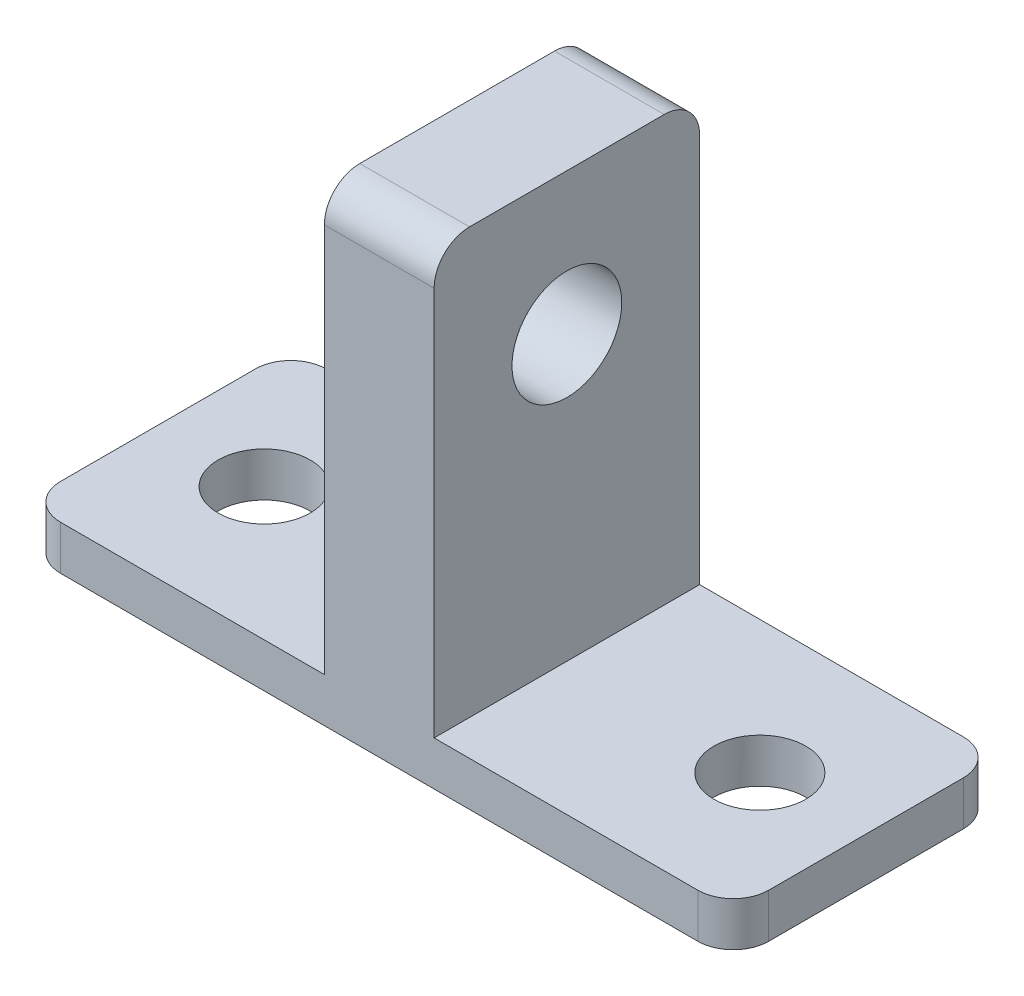
SolidWorks part; units mm, degrees
ref_plane "Front Plane" through (0, 0, 0) normal (0, 0, 1) x (1, 0, 0)
ref_plane "Top Plane" through (0, 0, 0) normal (0, 1, 0) x (1, 0, 0)
ref_plane "Right Plane" through (0, 0, 0) normal (1, 0, 0) x (0, 0, -1)
sketch "Sketch1" plane through (0, 0, 0) normal (0, 1, 0) x (1, 0, 0)
  line L1 (-25.4, 9.525) -> (25.4, 9.525)
  line L2 (-25.4, 9.525) -> (-25.4, -9.525)
  line L3 (-25.4, -9.525) -> (25.4, -9.525)
  line L4 (25.4, 9.525) -> (25.4, -9.525)
  line L5 (-25.4, 9.525) -> (25.4, -9.525) construction
  line L6 (-25.4, -9.525) -> (25.4, 9.525) construction
  point P0 (0, 0)
  dimension "D1" = 50.8
  dimension "D2" = 19.05
extrude "Boss-Extrude1" add sketch "Sketch1" along normal blind 3.175
sketch "Sketch2" plane through (0, 3.175, 0) normal (0, 1, 0) x (1, 0, 0)
  line L5 (-25.4, -9.525) -> (25.4, -9.525) construction
  line L6 (-3.937, 9.525) -> (3.937, 9.525)
  line L8 (0, -1000) -> (0, 49000) construction
  line L9 (-3.937, 9.525) -> (-3.937, -9.525)
  line L10 (-3.937, -9.525) -> (3.937, -9.525)
  line L15 (3.937, 9.525) -> (3.937, -9.525)
  line L16 (-3.937, 9.525) -> (3.937, -9.525) construction
  line L17 (-3.937, -9.525) -> (3.937, 9.525) construction
  point P0 (0, 0)
  dimension "D1" = 7.874
extrude "Boss-Extrude2" add sketch "Sketch2" along normal blind 30.48
sketch "Sketch3" plane through (3.937, 0, 0) normal (1, 0, 0) x (0, 0, -1)
  line L0 (9.525, 33.655) -> (9.525, 3.175) construction
  line L12 (-9.525, 33.655) -> (9.525, 33.655) construction
  line L13 (-9.525, 33.655) -> (-9.525, 23.495) construction
  line L14 (-9.525, 23.495) -> (9.525, 23.495) construction
  line L15 (9.525, 33.655) -> (9.525, 23.495) construction
  line L16 (0, 23.495) -> (0, 33.655) construction
  line L17 (-9.525, 28.575) -> (9.525, 28.575) construction
  circle A1 centre (0, 23.495) radius 3.937
  point P145 (0, 28.575)
  dimension "D1" = 10.16
  dimension "0.305" = 7.874
extrude "Cut-Extrude1" cut sketch "Sketch3" against normal through all both and the other way through all
sketch "Sketch5" plane through (0, 3.175, 0) normal (0, 1, 0) x (1, 0, 0)
  line L5 (-25.4, -9.525) -> (-3.937, -9.525) construction
  line L6 (-25.4, 9.525) -> (-17.78, 9.525) construction
  line L11 (-25.4, 9.525) -> (-25.4, -9.525) construction
  line L12 (-25.4, -9.525) -> (-17.78, -9.525) construction
  line L17 (-17.78, 9.525) -> (-17.78, -9.525) construction
  line L18 (-21.59, -9.525) -> (-21.59, 9.525) construction
  line L19 (-25.4, 0) -> (-17.78, 0) construction
  line L20 (0, -10.4775) -> (0, 10.4775) construction
  line L21 (25.4, 0) -> (17.78, 0) construction
  line L22 (21.59, -9.525) -> (21.59, 9.525) construction
  line L23 (17.78, 9.525) -> (17.78, -9.525) construction
  line L24 (25.4, -9.525) -> (17.78, -9.525) construction
  line L25 (25.4, 9.525) -> (25.4, -9.525) construction
  line L26 (25.4, 9.525) -> (17.78, 9.525) construction
  circle A2 centre (-17.78, 0) radius 3.302
  circle A3 centre (17.78, 0) radius 3.302
  point P18 (21.59, 0)
  point P338 (-21.59, 0)
  dimension "D1" = 7.62
  dimension "D2" = 6.604
extrude "Cut-Extrude2" cut sketch "Sketch5" against normal through all both and the other way through all
fillet "Fillet2" radius 2.54 6 edges at (-25.4, 1.5875, -9.525) (25.4, 1.5875, -9.525) (25.4, 1.5875, 9.525) (-25.4, 1.5875, 9.525) (0, 33.655, -9.525) (0, 33.655, 9.525)
ref_axis "Axis1" through (0, 0, 0) along (0, 1, 0)
ref_axis "Axis2" through (-3.937, 23.495, 0) along (1, 0, 0)
ref_point "Point2"
